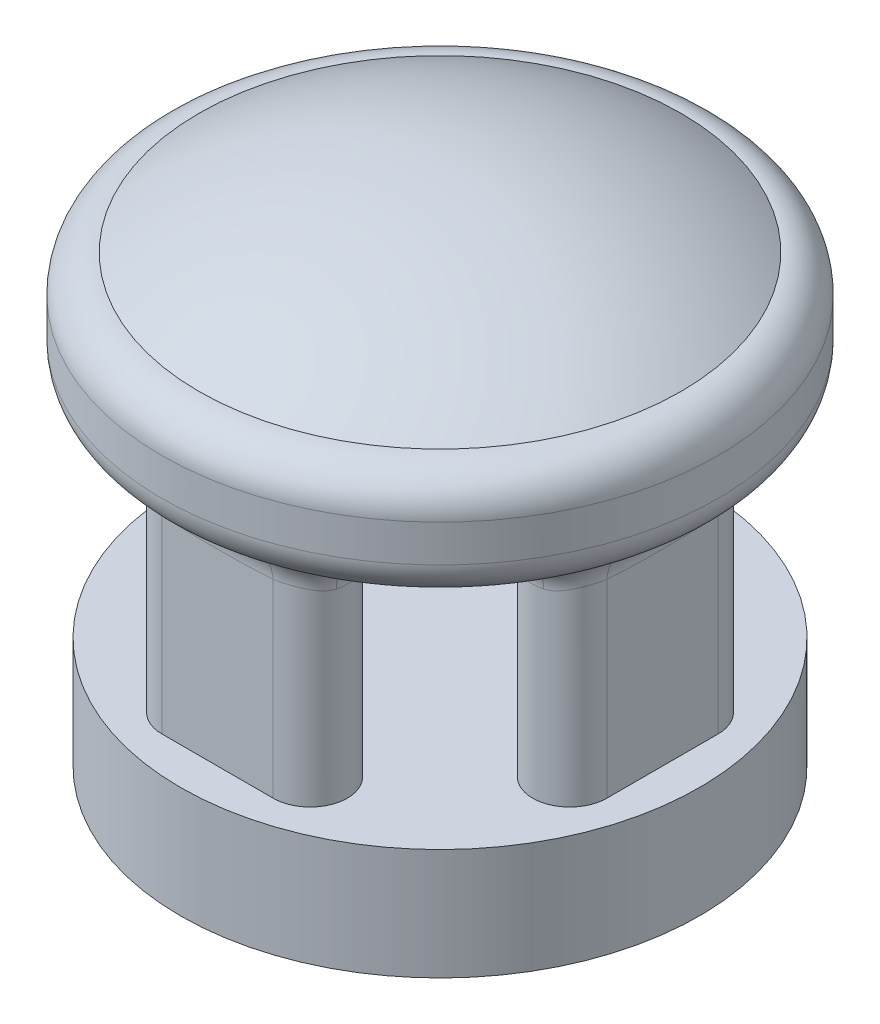
SolidWorks part; units mm, degrees
ref_plane "Front Plane" through (0, 0, 0) normal (0, 0, 1) x (1, 0, 0)
ref_plane "Top Plane" through (0, 0, 0) normal (0, 1, 0) x (1, 0, 0)
ref_plane "Right Plane" through (0, 0, 0) normal (1, 0, 0) x (0, 0, -1)
sketch "Sketch1" plane through (0, 0, 0) normal (0, 1, 0) x (1, 0, 0)
  circle A0 centre (0, 0) radius 9.525
  dimension "D1" = 19.05
extrude "button top" add sketch "Sketch1" along normal blind 3.81
sketch "Sketch2" plane through (0, 0, 0) normal (0, -1, 0) x (1, 0, 0)
  line L9 (-1.905, 6.35) -> (1.905, 6.35) construction
  line L10 (-1.905, 7.62) -> (1.905, 7.62)
  line L11 (-1.905, 5.08) -> (1.905, 5.08)
  arc A6 (-1.905, 7.62) -> (-1.905, 5.08) centre (-1.905, 6.35) ccw
  arc A7 (1.905, 5.08) -> (1.905, 7.62) centre (1.905, 6.35) ccw
  point P22 (0, 6.35)
  dimension "D2" = 1.27
  dimension "D1" = 6.35
  dimension "D8" = 3.81
extrude "connecting leg" add sketch "Sketch2" along normal blind 7.62
ref_axis "central axis" through (0, 3.81, 0) along (0, -1, 0)
pattern_circular "moar legs" count 4 over 360 about axis through (0, 3.81, 0) along (0, -1, 0) of "connecting leg"
ref_plane "base plane" through (0, -7.62, 0) normal (0, -1, 0) x (-1, 0, 0)
sketch "Sketch3" plane through (0, -7.62, 0) normal (0, -1, 0) x (-1, 0, 0)
  circle A0 centre (0, 0) radius 8.89
extrude "base" add sketch "Sketch3" along normal blind 3.81
fillet "round top" radius 1.27 2 edges at (0, 3.81, 9.525) (0, 0, 9.525)
fillet "round bars" radius 1.27 16 edges at (0, 0, 5.08) (-3.175, 0, 6.35) (0, 0, 7.62) (3.175, 0, 6.35) (5.08, 0, 0) (6.35, 0, 3.175) (7.62, 0, 0) (6.35, 0, -3.175) (3.175, 0, -6.35) (0, 0, -7.62) (-3.175, 0, -6.35) (0, 0, -5.08) (-5.08, 0, 0) (-6.35, 0, -3.175) (-7.62, 0, 0) (-6.35, 0, 3.175)
dome "button ness" faces to dome 1 distance 2.54 reverse direction no elliptical dome no face at (0, 3.81, 8.255) parameters "D1"=2.54
ref_point "center of face"
sketch "Sketch6" plane through (0, -11.43, 0) normal (0, -1, 0) x (1, 0, 0)
  circle A0 centre (0, 0) radius 2.54
extrude "flag" add sketch "Sketch6" along normal blind 2.54
fillet "flag fillet" radius 2.54 1 edges at (0, -11.43, -2.54)
